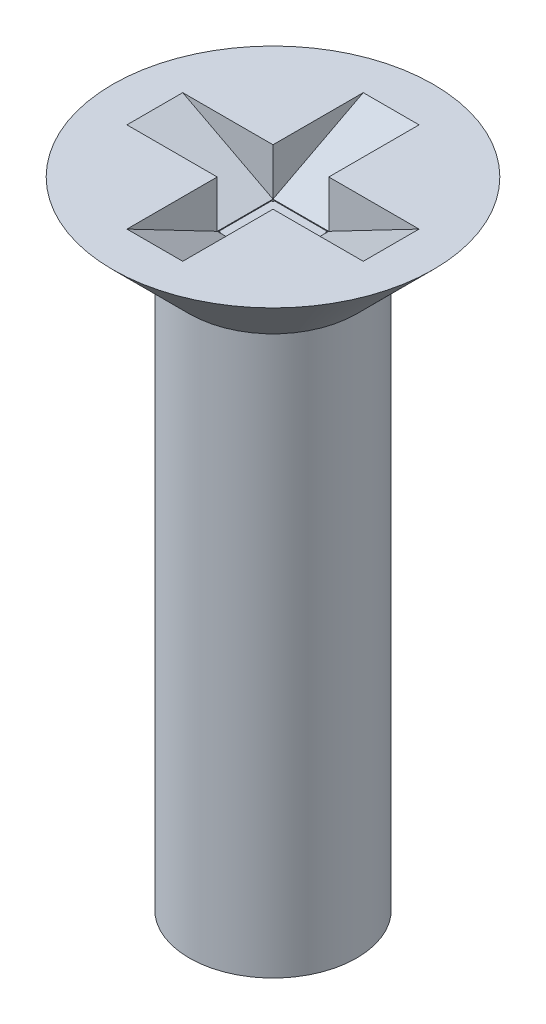
SolidWorks part; units mm, degrees
ref_plane "Спереди" through (0, 0, 0) normal (0, 0, 1) x (1, 0, 0)
ref_plane "Сверху" through (0, 0, 0) normal (0, 1, 0) x (1, 0, 0)
ref_plane "Справа" through (0, 0, 0) normal (1, 0, 0) x (0, 0, -1)
ref_axis "Axis1" through (0, 0, 0) along (0, 1, 0)
sketch "Sketch1" plane through (0, 0, 0) normal (0, 0, 1) x (1, 0, 0)
  line L0 (0, 0) -> (0, -6966.8706) construction
  line L1 (-1.5, 0) -> (-1.5, -10)
  line L2 (-1.5, -10) -> (0, -10)
  line L3 (0, -10) -> (0, 1.375)
  line L4 (0, 1.375) -> (-2.875, 1.375)
  line L5 (-2.875, 1.375) -> (-1.5, 0)
  dimension "D1" = 10
  dimension "D2" = 3
  dimension "D3" = 45
  dimension "D4" = 5.75
revolve "Revolve1" add sketch "Sketch1" angle 360 about L0
sketch "Sketch2" plane through (0, 0, 0) normal (0, 0, 1) x (1, 0, 0)
  line L0 (-2.1178, 1.375) -> (2.1178, 1.375)
  line L1 (2.875, 1.375) -> (-2.875, 1.375) construction
  line L2 (2.1178, 1.375) -> (0.4726, 0.517)
  line L3 (0.4726, 0.517) -> (-0.4726, 0.517)
  line L4 (-0.4726, 0.517) -> (-2.1178, 1.375)
  point P6 (0, 1.375)
extrude "Cut-Extrude1" cut sketch "Sketch2" against normal mid plane 1
pattern_circular "CirPattern1" count 4 over 360 about axis through (0, 0, 0) along (0, 1, 0) of "Cut-Extrude1"
